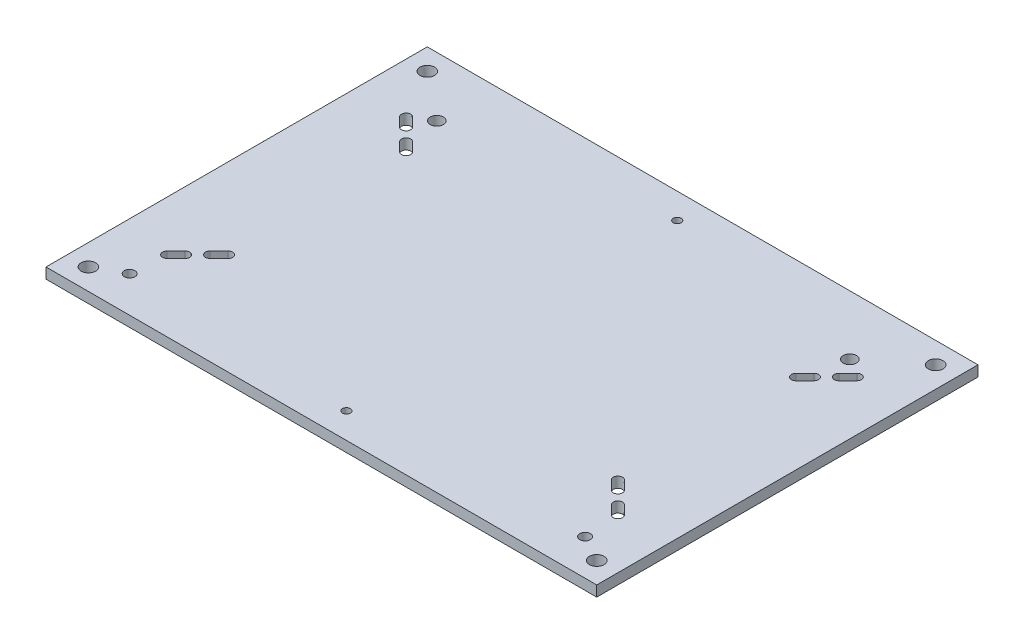
SolidWorks part; units mm, degrees
ref_plane "Front Plane" through (0, 0, 0) normal (0, 0, 1) x (1, 0, 0)
ref_plane "Top Plane" through (0, 0, 0) normal (0, 1, 0) x (1, 0, 0)
ref_plane "Right Plane" through (0, 0, 0) normal (1, 0, 0) x (0, 0, -1)
sketch "Sketch1" plane through (0, 0, 0) normal (0, 1, 0) x (1, 0, 0)
  line L1 (0, 0) -> (330.2, 0)
  line L2 (0, 0) -> (0, -228.6)
  line L3 (0, -228.6) -> (330.2, -228.6)
  line L4 (330.2, 0) -> (330.2, -228.6)
  dimension "D1" = 330.2
  dimension "D2" = 228.6
extrude "base plate" add sketch "Sketch1" against normal blind 6.35
sketch "center lines" plane through (0, 0, 0) normal (0, 1, 0) x (1, 0, 0)
  line L0 (165.1, 0) -> (165.1, -228.6) construction
  line L1 (330.2, 0) -> (0, 0) construction
  line L2 (0, -228.6) -> (330.2, -228.6) construction
  line L3 (0, -114.3) -> (330.2, -114.3) construction
  line L4 (0, 0) -> (0, -228.6) construction
  line L5 (330.2, -228.6) -> (330.2, 0) construction
sketch "Sketch3" plane through (0, 0, 0) normal (0, 1, 0) x (1, 0, 0)
  line L0 (21.0672, -185.8525) -> (30.0475, -194.8328)
  line L1 (30.0475, -194.8328) -> (60.5804, -164.2999)
  line L2 (60.5804, -164.2999) -> (51.6001, -155.3196)
  line L3 (51.6001, -155.3196) -> (21.0672, -185.8525)
  line L4 (29.9612, -185.9388) -> (35.3494, -180.5506) construction
  line L5 (28.0167, -183.9942) -> (33.4048, -178.6061)
  line L6 (31.9058, -187.8833) -> (37.2939, -182.4952)
  line L7 (0, -228.6) -> (330.2, -228.6) construction
  line L8 (48.2187, -167.6813) -> (42.8306, -173.0694) construction
  line L9 (50.1633, -169.6258) -> (44.7751, -175.014)
  line L10 (165.1, 0) -> (165.1, -228.6) construction
  line L11 (0, -114.3) -> (330.2, -114.3) construction
  line L12 (60.5804, -64.3001) -> (51.6001, -73.2804)
  line L13 (30.0475, -33.7672) -> (60.5804, -64.3001)
  line L14 (21.0672, -42.7475) -> (30.0475, -33.7672)
  line L15 (51.6001, -73.2804) -> (21.0672, -42.7475)
  line L16 (300.1525, -33.7672) -> (269.6196, -64.3001)
  line L17 (309.1328, -42.7475) -> (300.1525, -33.7672)
  line L18 (278.5999, -73.2804) -> (309.1328, -42.7475)
  line L19 (269.6196, -64.3001) -> (278.5999, -73.2804)
  line L20 (269.6196, -164.2999) -> (278.5999, -155.3196)
  line L21 (300.1525, -194.8328) -> (269.6196, -164.2999)
  line L22 (309.1328, -185.8525) -> (300.1525, -194.8328)
  line L23 (278.5999, -155.3196) -> (309.1328, -185.8525)
  line L24 (46.2742, -165.7367) -> (40.886, -171.1249)
  line L25 (29.9612, -42.6612) -> (35.3494, -48.0494) construction
  line L26 (28.0167, -44.6058) -> (33.4048, -49.9939)
  line L27 (31.9058, -40.7167) -> (37.2939, -46.1048)
  line L28 (48.2187, -60.9187) -> (42.8306, -55.5306) construction
  line L29 (50.1633, -58.9742) -> (44.7751, -53.586)
  line L30 (46.2742, -62.8633) -> (40.886, -57.4751)
  line L31 (300.2388, -42.6612) -> (294.8506, -48.0494) construction
  line L32 (302.1833, -44.6058) -> (296.7952, -49.9939)
  line L33 (298.2942, -40.7167) -> (292.9061, -46.1048)
  line L34 (281.9813, -60.9187) -> (287.3694, -55.5306) construction
  line L35 (280.0367, -58.9742) -> (285.4249, -53.586)
  line L36 (283.9258, -62.8633) -> (289.314, -57.4751)
  line L37 (281.9813, -167.6813) -> (287.3694, -173.0694) construction
  line L38 (280.0367, -169.6258) -> (285.4249, -175.014)
  line L39 (283.9258, -165.7367) -> (289.314, -171.1249)
  line L40 (300.2388, -185.9388) -> (294.8506, -180.5506) construction
  line L41 (302.1833, -183.9942) -> (296.7952, -178.6061)
  line L42 (298.2942, -187.8833) -> (292.9061, -182.4952)
  line L43 (51.6001, -164.2999) -> (51.6001, -155.3196)
  line L44 (60.5804, -164.2999) -> (51.6001, -164.2999)
  line L45 (51.6001, -64.3001) -> (51.6001, -73.2804)
  line L46 (60.5804, -64.3001) -> (51.6001, -64.3001)
  line L47 (278.5999, -64.3001) -> (278.5999, -73.2804)
  line L48 (269.6196, -64.3001) -> (278.5999, -64.3001)
  line L49 (278.5999, -164.2999) -> (278.5999, -155.3196)
  line L50 (269.6196, -164.2999) -> (278.5999, -164.2999)
  arc A0 (28.0167, -183.9942) -> (31.9058, -187.8833) centre (29.9612, -185.9388) ccw
  arc A1 (37.2939, -182.4952) -> (33.4048, -178.6061) centre (35.3494, -180.5506) ccw
  arc A2 (50.1633, -169.6258) -> (46.2742, -165.7367) centre (48.2187, -167.6813) ccw
  arc A3 (40.886, -171.1249) -> (44.7751, -175.014) centre (42.8306, -173.0694) ccw
  arc A4 (28.0167, -44.6058) -> (31.9058, -40.7167) centre (29.9612, -42.6612) cw
  arc A5 (37.2939, -46.1048) -> (33.4048, -49.9939) centre (35.3494, -48.0494) cw
  arc A6 (50.1633, -58.9742) -> (46.2742, -62.8633) centre (48.2187, -60.9187) cw
  arc A7 (40.886, -57.4751) -> (44.7751, -53.586) centre (42.8306, -55.5306) cw
  arc A8 (302.1833, -44.6058) -> (298.2942, -40.7167) centre (300.2388, -42.6612) ccw
  arc A9 (292.9061, -46.1048) -> (296.7952, -49.9939) centre (294.8506, -48.0494) ccw
  arc A10 (280.0367, -58.9742) -> (283.9258, -62.8633) centre (281.9813, -60.9187) ccw
  arc A11 (289.314, -57.4751) -> (285.4249, -53.586) centre (287.3694, -55.5306) ccw
  arc A12 (280.0367, -169.6258) -> (283.9258, -165.7367) centre (281.9813, -167.6813) cw
  arc A13 (289.314, -171.1249) -> (285.4249, -175.014) centre (287.3694, -173.0694) cw
  arc A14 (302.1833, -183.9942) -> (298.2942, -187.8833) centre (300.2388, -185.9388) cw
  arc A15 (292.9061, -182.4952) -> (296.7952, -178.6061) centre (294.8506, -180.5506) cw
  point P29 (32.6553, -183.2447)
  point P36 (45.5246, -170.3754)
  point P44 (32.6553, -45.3553)
  point P51 (45.5246, -58.2246)
  point P58 (297.5447, -45.3553)
  point P65 (284.6754, -58.2246)
  point P72 (284.6754, -170.3754)
  point P79 (297.5447, -183.2447)
  point P84 (37.2939, -178.6061)
  point P85 (40.886, -175.014)
  dimension "D6" = 2.75
  dimension "D10" = 5.08
  dimension "D9" = 2.032
  dimension "D1" = 43.18
  dimension "D2" = 12.7
  dimension "D3" = 45
  dimension "D4" = 99.9998
  dimension "D5" = 226.9998
  dimension "D7" = 7.62
  dimension "D8" = 6.35
extrude "slots" cut sketch "Sketch3" against normal through all contours A5 L27 A4 L26 | L33 A9 L32 A8 | L36 A11 L35 A10 | A13 L39 A12 L38 | A15 L42 A14 L41 | L6 A1 L5 A0 | L24 A3 L9 A2 | L30 A7 L29 A6 region at (32.6553, 0, 45.3553) region at (297.5447, 0, 45.3553) region at (284.6754, 0, 58.2246) region at (284.6754, 0, 170.3754) region at (297.5447, 0, 183.2447)
sketch "location of ESD" [suppressed] plane through (0, 0, 0) normal (0, 1, 0) x (1, 0, 0)
  line L0 (330.2, -228.6) -> (330.2, 0) construction
  line L1 (330.2, 0) -> (0, 0) construction
  point P0 (304.8, -114.3)
  point P3 (330.2, -114.3)
  dimension "D1" = 25.4
  dimension "D2" = 114.3
hole_wizard "Feet connection hole" positions "Sketch6" profile "Sketch7" hole size "1/4-20" standard "PEM® Inch" end condition through all
sketch "Sketch6" plane through (0, 0, 0) normal (0, 1, 0) x (1, 0, 0)
  line L0 (0, -228.6) -> (330.2, -228.6) construction
  line L1 (0, 0) -> (0, -228.6) construction
  line L2 (330.2, -228.6) -> (330.2, 0) construction
  line L3 (330.2, 0) -> (0, 0) construction
  point P3 (12.7, -215.9)
  point P19 (317.5, -12.7)
  point P31 (317.5, -215.9)
  point P33 (12.7, -12.7)
  dimension "D1" = 12.7
  dimension "D2" = 12.7
  dimension "D3" = 12.7
  dimension "D4" = 12.7
sketch "Sketch7" plane through (12.7, 0, 215.9) normal (1, 0, 0) x (0, 0, 1)
  line L0 (0, 0) -> (0, 6.35)
  line L1 (0, 6.35) -> (4.3688, 6.35)
  line L2 (4.3688, 6.35) -> (4.3688, 0)
  line L5 (4.3688, 0) -> (0, 0)
  line L11 (0, -6.35) -> (0, 107.95) construction
  dimension "Thru Hole Dia." = 8.7376
  dimension "Thru Hole Depth" = 6.35
sketch "Vacuum Chamber base hole locations" plane through (0, 0, 0) normal (0, 1, 0) x (1, 0, 0)
  line L2 (330.2, -228.6) -> (330.2, 0) construction
  line L4 (330.2, 0) -> (0, 0) construction
  point P0 (41.275, -35.56)
  point P1 (288.925, -35.56)
  point P2 (301.625, -207.01)
  point P3 (28.575, -207.01)
  dimension "D1" = 247.65
  dimension "D2" = 12.7
  dimension "D3" = 12.7
  dimension "D4" = 171.45
  dimension "D5" = 28.575
  dimension "D6" = 35.56
  dimension "D7" = 0
  dimension "D8" = 171.45
hole_wizard "1/4 (0.25) Diameter Hole1" positions "Sketch9" profile "Sketch10" hole size "1/4" standard "ANSI Inch" end condition through all
sketch "Sketch9" plane through (0, 0, 0) normal (0, 1, 0) x (1, 0, 0)
  point P0 (28.575, -207.01)
  point P3 (301.625, -207.01)
sketch "Sketch10" plane through (28.575, 0, 207.01) normal (1, 0, 0) x (0, 0, 1)
  line L0 (0, 0) -> (0, 6.35)
  line L1 (0, 6.35) -> (3.175, 6.35)
  line L2 (3.175, 6.35) -> (3.175, 0)
  line L5 (3.175, 0) -> (0, 0)
  line L11 (0, -6.35) -> (0, 107.95) construction
  dimension "Thru Hole Dia." = 6.35
  dimension "Thru Hole Depth" = 6.35
hole_wizard "5/16 (0.3125) Diameter Hole1" positions "Sketch11" profile "Sketch12" hole size "5/16" standard "ANSI Inch" end condition through all
sketch "Sketch11" plane through (0, 0, 0) normal (0, 1, 0) x (1, 0, 0)
  point P0 (41.275, -35.56)
  point P3 (288.925, -35.56)
sketch "Sketch12" plane through (41.275, 0, 35.56) normal (1, 0, 0) x (0, 0, 1)
  line L0 (0, 0) -> (0, 6.35)
  line L1 (0, 6.35) -> (3.9687, 6.35)
  line L2 (3.9687, 6.35) -> (3.9687, 0)
  line L5 (3.9687, 0) -> (0, 0)
  line L11 (0, -6.35) -> (0, 107.95) construction
  dimension "Thru Hole Dia." = 7.9375
  dimension "Thru Hole Depth" = 6.35
sketch "Sketch14" plane through (0, 0, 0) normal (0, 1, 0) x (1, 0, 0)
  line L2 (0, 0) -> (0, -228.6) construction
  line L3 (330.2, 0) -> (0, 0) construction
  line L4 (0, -228.6) -> (330.2, -228.6) construction
  point P0 (165.1, -15.24)
  point P1 (165.1, -213.36)
  dimension "D1" = 165.1
  dimension "D2" = 15.24
  dimension "D3" = 165.1
  dimension "D4" = 15.24
hole_wizard "ESD Connection hole" positions "Sketch15" profile "Sketch16" hole size "#6-32" standard "PEM® Inch" end condition through all
sketch "Sketch15" plane through (0, 0, 0) normal (0, 1, 0) x (1, 0, 0)
  point P0 (165.1, -15.24)
  point P3 (164.7687, -213.267)
sketch "Sketch16" plane through (165.1, 0, 15.24) normal (1, 0, 0) x (0, 0, 1)
  line L0 (0, 0) -> (0, 6.35)
  line L1 (0, 6.35) -> (2.3812, 6.35)
  line L2 (2.3812, 6.35) -> (2.3812, 0)
  line L5 (2.3812, 0) -> (0, 0)
  line L11 (0, -6.35) -> (0, 107.95) construction
  dimension "Thru Hole Dia." = 4.7625
  dimension "Thru Hole Depth" = 6.35
